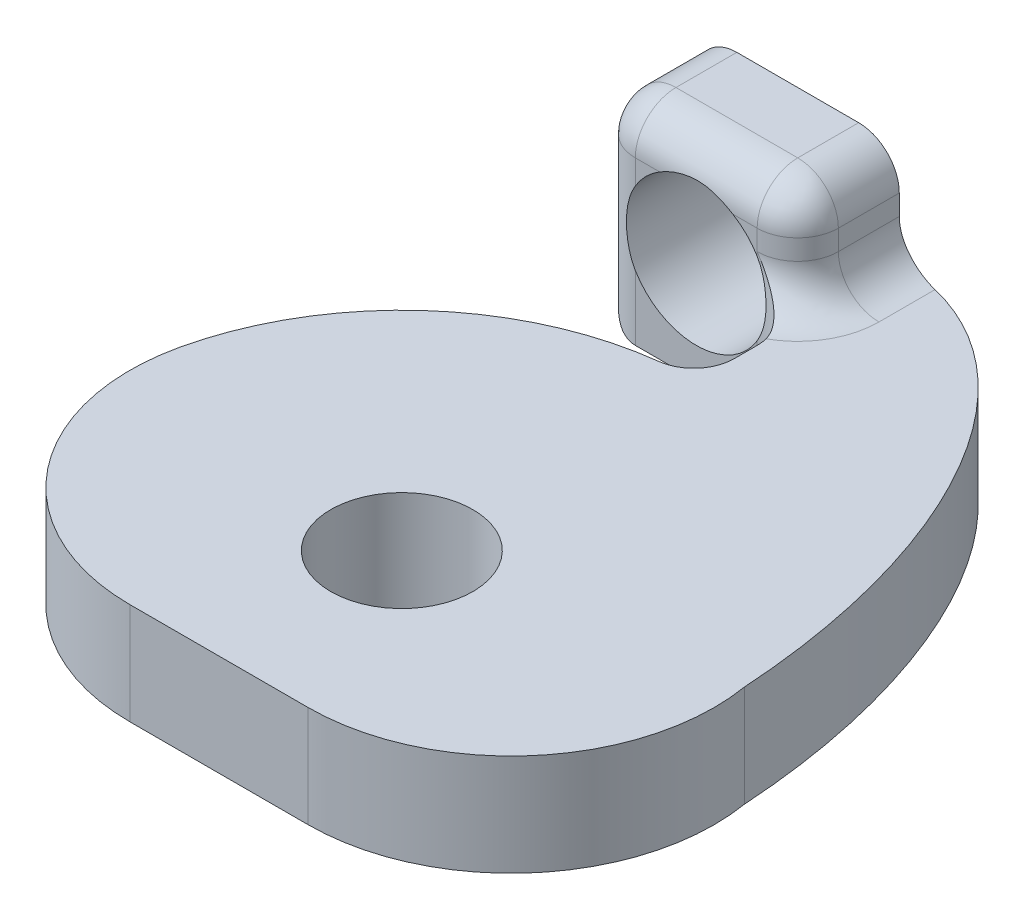
SolidWorks part; units mm, degrees
ref_plane "Front Plane" through (0, 0, 0) normal (0, 0, 1) x (1, 0, 0)
ref_plane "Top Plane" through (0, 0, 0) normal (0, 1, 0) x (1, 0, 0)
ref_plane "Right Plane" through (0, 0, 0) normal (1, 0, 0) x (0, 0, -1)
sketch "Sketch1" plane through (0, 0, 0) normal (0, 1, 0) x (1, 0, 0)
  line L0 (0, 14.5) -> (0, 24.5) construction
  line L1 (-4.3875, -9) -> (4.3875, -9)
  line L2 (0, 24.5) -> (-10, 24.5)
  line L3 (-10, 24.5) -> (-10, 19.5)
  line L4 (-10, 19.5) -> (-2, 19.5)
  line L5 (0, 17.5) -> (0, 16.3783)
  arc A0 (-1.7576, 14.3931) -> (-14.1374, 3.2222) centre (0, 0) ccw
  arc A1 (-14.1374, 3.2222) -> (-4.3875, -9) centre (-4.3875, 1) ccw
  arc A2 (14.255, 2.6225) -> (4.3875, -9) centre (4.3875, 1) cw
  circle A3 centre (0, 0) radius 3.5
  arc A4 (0, 16.3783) -> (-1.7576, 14.3931) centre (-2, 16.3783) cw
  arc A5 (0, 17.5) -> (-2, 19.5) centre (-2, 17.5) ccw
  ellipse E1 centre (0, 0) end of major axis (0, 24.5) minor radius 14.3374 (14.255, 2.6225) -> (0, 24.5) ccw
  point P30 (0, 19.5)
  dimension "D1" = 29
  dimension "D2" = 10
  dimension "D3" = 10
  dimension "D4" = 7
  dimension "D7" = 2
  dimension "D8" = 2
  dimension "D5" = 10
  dimension "D6" = 10
extrude "Boss-Extrude1" add sketch "Sketch1" along normal blind 5
sketch "Sketch2" plane through (0, 0, -24.5) normal (0, 0, -1) x (-1, 0, 0)
  line L0 (0, 5) -> (10, 5)
  line L2 (0, 5) -> (0, 10)
  line L3 (0, 10) -> (10, 10)
  line L4 (10, 5) -> (10, 10)
extrude "Boss-Extrude2" add sketch "Sketch2" against normal blind 5
fillet "Fillet1" radius 2 6 edges at (0, 7.5, -19.5) (-5, 10, -19.5) (-10, 5, -19.5) (-10, 0, -22) (-10, 10, -22) (0, 10, -22)
fillet "Fillet2" radius 2 2 edges at (-0.5858, 5, -20.0858) (0, 5, -23)
sketch "Sketch3" plane through (0, 0, -24.5) normal (0, 0, -1) x (-1, 0, 0)
  line L0 (10, 5) -> (0, 5) construction
  line L1 (10, 8) -> (10, 2) construction
  line L2 (0, 7) -> (0, 0) construction
  circle A0 centre (5, 5) radius 3.5
  dimension "D1" = 7
extrude "Cut-Extrude1" cut sketch "Sketch3" against normal up to next
